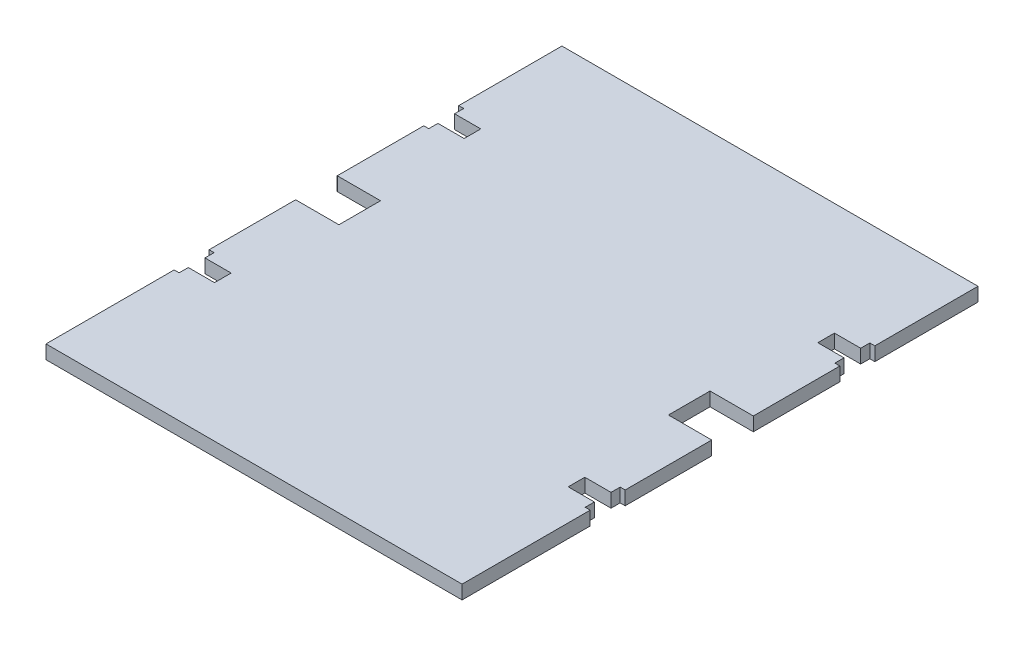
SolidWorks part; units mm, degrees
ref_plane "Front Plane" through (0, 0, 0) normal (0, 0, 1) x (1, 0, 0)
ref_plane "Top Plane" through (0, 0, 0) normal (0, 1, 0) x (1, 0, 0)
ref_plane "Right Plane" through (0, 0, 0) normal (1, 0, 0) x (0, 0, -1)
sketch "Sketch1" plane through (0, 0, 0) normal (0, 1, 0) x (1, 0, 0)
  line L1 (-250, -310) -> (250, -310)
  line L2 (-250, -310) -> (-250, 310)
  line L3 (-250, 310) -> (250, 310)
  line L4 (250, -310) -> (250, 310)
  line L5 (-250, -310) -> (250, 310) construction
  line L6 (-250, 310) -> (250, -310) construction
  point P0 (0, 0)
  dimension "D1" = 500
  dimension "D2" = 620
extrude "Boss-Extrude1" add sketch "Sketch1" along normal blind 16.5
sketch "Sketch2" plane through (0, 16.5, 0) normal (0, 1, 0) x (1, 0, 0)
  line L0 (-250, 310) -> (-250, -310) construction
  line L1 (-250, 40) -> (-198, 40)
  line L2 (-250, 40) -> (-250, -10)
  line L3 (-250, -10) -> (-198, -10)
  line L4 (-198, 40) -> (-198, -10)
  line L5 (250, -310) -> (250, 310) construction
  line L6 (250, 40) -> (198, 40)
  line L7 (250, 40) -> (250, -10)
  line L8 (250, -10) -> (198, -10)
  line L9 (198, 40) -> (198, -10)
  line L10 (250, 310) -> (-250, 310) construction
  line L11 (0, 310) -> (0, -310) construction
  line L12 (-250, 186) -> (-244, 186)
  line L13 (-250, 186) -> (-250, 144)
  line L14 (-250, 144) -> (-244, 144)
  line L15 (-244, 186) -> (-244, 175)
  line L16 (-244, 175) -> (-212.5, 175)
  line L18 (-244, 155) -> (-212.5, 155)
  line L19 (-212.5, 175) -> (-212.5, 155)
  line L20 (-250, -310) -> (250, -310) construction
  line L21 (-92.6056, 0) -> (108.2015, 0) construction
  line L22 (212.5, 175) -> (212.5, 155)
  line L23 (244, 155) -> (212.5, 155)
  line L25 (244, 175) -> (212.5, 175)
  line L26 (244, 186) -> (244, 175)
  line L27 (250, 144) -> (244, 144)
  line L28 (250, 186) -> (250, 144)
  line L29 (250, 186) -> (244, 186)
  line L46 (212.5, -125) -> (212.5, -145)
  line L47 (-250, -114) -> (-244, -114)
  line L48 (-250, -114) -> (-250, -156)
  line L49 (-250, -156) -> (-244, -156)
  line L50 (-244, -114) -> (-244, -125)
  line L51 (-244, -125) -> (-212.5, -125)
  line L53 (-244, -145) -> (-212.5, -145)
  line L54 (-212.5, -125) -> (-212.5, -145)
  line L55 (244, -145) -> (212.5, -145)
  line L57 (244, -125) -> (212.5, -125)
  line L58 (244, -114) -> (244, -125)
  line L59 (250, -156) -> (244, -156)
  line L60 (250, -114) -> (250, -156)
  line L61 (250, -114) -> (244, -114)
  line L62 (-244, 155) -> (-244, 144)
  line L63 (244, 155) -> (244, 144)
  line L64 (244, -145) -> (244, -156)
  line L65 (-244, -145) -> (-244, -156)
  dimension "D1" = 270
  dimension "D2" = 50
  dimension "D3" = 52
  dimension "D4" = 52
  dimension "D5" = 50
  dimension "D6" = 270
  dimension "D7" = 124
  dimension "D8" = 42
  dimension "D9" = 6
  dimension "D10" = 31.5
  dimension "D11" = 20
  dimension "D12" = 6
  dimension "D13" = 42
  dimension "D14" = 31.5
  dimension "D15" = 20
  dimension "D16" = 154
extrude "Cut-Extrude1" cut sketch "Sketch2" against normal through all
